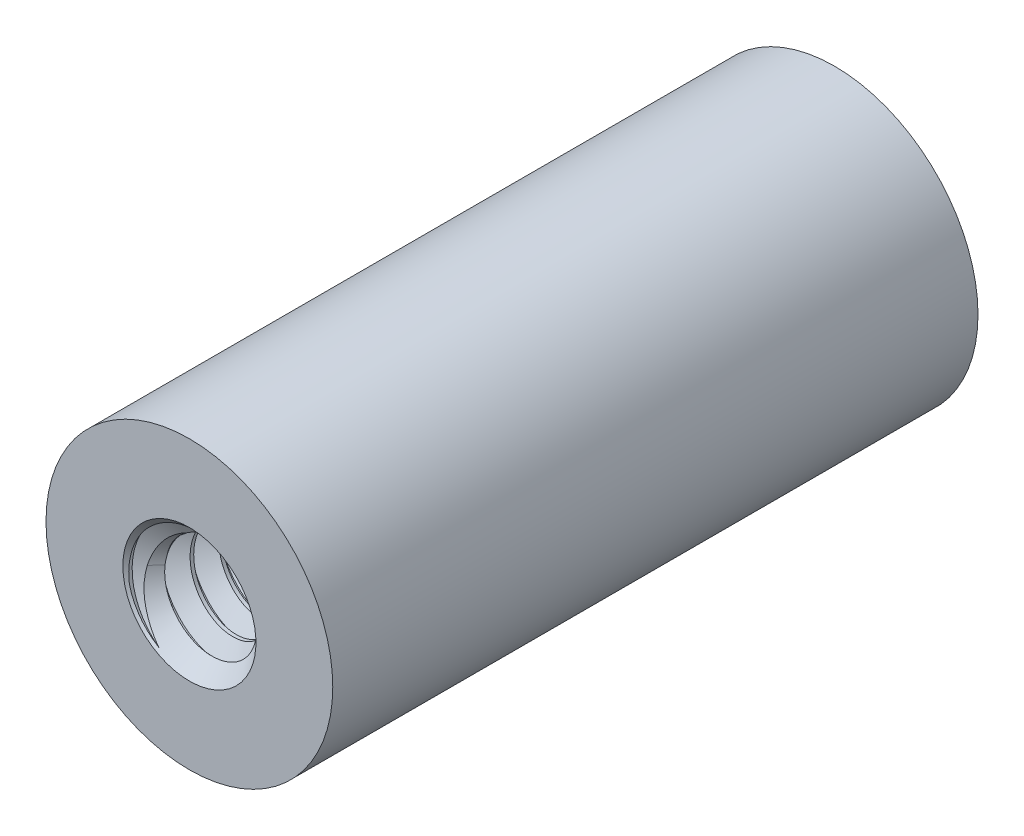
SolidWorks part; units mm, degrees
ref_plane "Front Plane" through (0, 0, 0) normal (0, 0, 1) x (1, 0, 0)
ref_plane "Top Plane" through (0, 0, 0) normal (0, 1, 0) x (1, 0, 0)
ref_plane "Right Plane" through (0, 0, 0) normal (1, 0, 0) x (0, 0, -1)
sketch "Sketch3" plane through (0, 0, 0) normal (1, 0, 0) x (0, 0, -1)
  line L0 (-7.1437, 0) -> (7.1437, 0) construction
  line L1 (0, 3.175) -> (0, -3.175) construction
  line L2 (-7.1437, 1.4224) -> (-7.1437, -1.4224) construction
  point P2 (-3.9687, 0)
  point P3 (3.9687, 0)
  dimension "Length" = 14.2875
  dimension "Min Thread Length" = 11.1125
  dimension "D1" = 11.1125
  dimension "Thread Dia" = 2.8448
  dimension "OD" = 6.35
sketch "Sketch1" plane through (0, 0, 0) normal (0, 0, 1) x (1, 0, 0)
  circle A1 centre (0, 0) radius 1.4224
  circle A2 centre (0, 0) radius 3.175
extrude "Extrude1" add sketch "Sketch1" along normal up to vertex (7.1437 mm away) and the other way up to vertex (7.1437 mm away) up to point (0, 0, 7.1437) other way up to point (0, 0, -7.1437)
sketch "Sketch11" plane through (0, 0, -7.1437) normal (0, 0, -1) x (-1, 0, 0)
  circle A0 centre (0, 0) radius 1.4224 construction
  circle A1 centre (0, 0) radius 1.4224
curve "Helix/Spiral1" pitch 0.635 height 14.9225 radius 1.4224 centre (0, 0, -7.1437) axis (0, 0, 1) start towards (0, 1, 0) parameters "Pitch"=0.635
sketch "Sketch12" plane through (0, 0, 0) normal (1, 0, 0) x (0, 0, -1)
  line L0 (7.6994, 1.4224) -> (7.1437, 1.4224)
  line L1 (7.6994, 1.4224) -> (7.4613, 1.01)
  line L2 (7.4613, 1.01) -> (7.3819, 1.01)
  line L3 (7.3819, 1.01) -> (7.1437, 1.4224)
  line L4 (7.4216, 1.01) -> (7.4216, 1.4224) construction
  line L5 (7.5803, 1.2162) -> (7.2628, 1.2162) construction
  dimension "D1" = 0.0794
  dimension "D2" = 0.3175
  dimension "D3" = 60
sweep "Sweep1" add profiles "Sketch12" path "Helix/Spiral1"
sketch "Sketch6" plane through (0, 0, -7.1437) normal (0, 0, -1) x (-1, 0, 0)
  circle A1 centre (0, 0) radius 3.175
  circle A2 centre (0, 0) radius 3.175
  dimension "D1" = 0
extrude "Extrude2" cut sketch "Sketch6" along normal through all
sketch "Sketch7" plane through (0, 0, -7.1437) normal (0, 0, -1) x (-1, 0, 0)
  circle A2 centre (0, 0) radius 1.4732
  circle A3 centre (0, 0) radius 1.4732
  dimension "D1" = 0.0508
extrude "Extrude3" cut sketch "Sketch7" against normal through all draft 43
mirror "Mirror1" about plane through (0, 0, 0) normal (0, 0, 1) of "Extrude2", "Extrude3"
sketch "Sketch9" [suppressed] plane through (0, 0, 0) normal (1, 0, 0) x (0, 0, -1)
  line L1 (-20.6375, 2.1336) -> (20.6375, 2.1336)
  line L2 (-20.6375, 2.1336) -> (-20.6375, 0)
  line L3 (-20.6375, 0) -> (20.6375, 0)
  line L4 (20.6375, 2.1336) -> (20.6375, 0)
  line L7 (-31.75, 0) -> (31.75, 0) construction
revolve "Revolve" [suppressed] add sketch "Sketch9" angle 360 about L0
sketch "Sketch10" [suppressed] plane through (0, 0, 0) normal (1, 0, 0) x (0, 0, -1)
  line L0 (31.75, 2.0828) -> (20.6375, 2.0828)
  line L1 (-31.75, 2.0828) -> (-20.6375, 2.0828)
  line L2 (20.6375, 2.0828) -> (20.6375, -2.0828)
  line L3 (-31.75, -2.1336) -> (-20.6375, -2.1336)
  line L4 (-20.6375, 2.0828) -> (-20.6375, -2.1336)
  line L5 (20.6375, -2.0828) -> (31.75, -2.0828)
equation "\"D1@Sketch3\" = \"Min Thread Length@Sketch3\""
equation "\"D3@Helix/Spiral1\" = \"Length@Sketch3\"+\"Pitch@Helix/Spiral1\""
equation "\"D1@Sketch12\" = \"Pitch@Helix/Spiral1\"*.125"
equation "\"D2@Sketch12\" = \"Pitch@Helix/Spiral1\"*.5"
